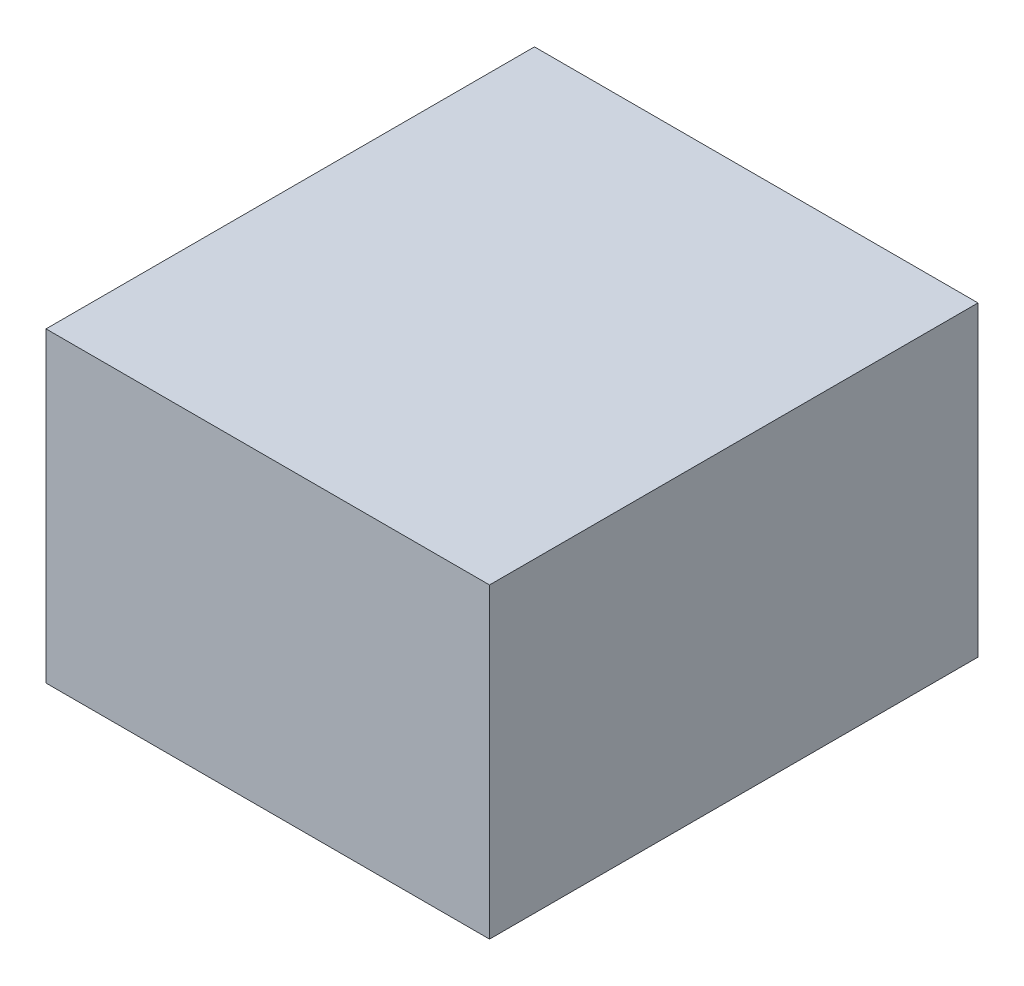
SolidWorks part; units mm, degrees
ref_plane "Front Plane" through (0, 0, 0) normal (0, 0, 1) x (1, 0, 0)
ref_plane "Top Plane" through (0, 0, 0) normal (0, 1, 0) x (1, 0, 0)
ref_plane "Right Plane" through (0, 0, 0) normal (1, 0, 0) x (0, 0, -1)
sketch "Sketch1" plane through (0, 0, 0) normal (0, 1, 0) x (1, 0, 0)
  line L1 (-45.4, -50) -> (45.4, -50)
  line L2 (-45.4, -50) -> (-45.4, 50)
  line L3 (-45.4, 50) -> (45.4, 50)
  line L4 (45.4, -50) -> (45.4, 50)
  line L5 (-45.4, -50) -> (45.4, 50) construction
  line L6 (-45.4, 50) -> (45.4, -50) construction
  point P0 (0, 0)
extrude "Boss-Extrude1" add sketch "Sketch1" along normal blind 62.8
sketch "Sketch2" plane through (0, 0, 0) normal (0, -1, 0) x (-1, 0, 0)
  line L1 (33.5507, -1.55) -> (33.5507, -5.4485)
  line L4 (-30.4478, 1.55) -> (-30.4478, 5.4485)
  line L12 (-30.4478, -5.4485) -> (-30.4478, -1.55)
  line L13 (-31.9993, 7) -> (-32, 7)
  line L14 (-33.5507, 5.4485) -> (-33.5507, 1.55)
  line L15 (-32, -7) -> (-31.9985, -7)
  line L17 (-33.5507, -1.55) -> (-33.5507, -5.4485)
  line L19 (-26.55, 1.55) -> (-30.4478, 1.55)
  line L21 (-37.45, -1.55) -> (-33.5507, -1.55)
  line L22 (-30.4478, -1.55) -> (-26.55, -1.55)
  line L23 (-33.5507, 1.55) -> (-37.45, 1.55)
  line L28 (37.45, -1.55) -> (33.5507, -1.55)
  line L29 (33.5507, 1.55) -> (37.45, 1.55)
  line L30 (33.5507, 5.4485) -> (33.5507, 1.55)
  line L31 (30.4478, 1.55) -> (30.4478, 5.4485)
  line L32 (26.55, 1.55) -> (30.4478, 1.55)
  line L33 (30.4478, -1.55) -> (26.55, -1.55)
  line L34 (30.4478, -5.4485) -> (30.4478, -1.55)
  arc A0 (-33.5507, -5.4485) -> (-30.4478, -5.4485) centre (-31.9993, -5.4485) ccw
  arc A1 (-33.5507, 5.4485) -> (-30.4478, 5.4485) centre (-31.9993, 5.4485) cw
  arc A2 (-26.55, -1.55) -> (-26.55, 1.55) centre (-26.55, 0) ccw
  arc A3 (-37.45, -1.55) -> (-37.45, 1.55) centre (-37.45, 0) cw
  arc A4 (33.5507, -5.4485) -> (30.4478, -5.4485) centre (31.9993, -5.4485) cw
  arc A5 (37.45, -1.55) -> (37.45, 1.55) centre (37.45, 0) ccw
  arc A6 (33.5507, 5.4485) -> (30.4478, 5.4485) centre (31.9993, 5.4485) ccw
  arc A7 (26.55, -1.55) -> (26.55, 1.55) centre (26.55, 0) cw
extrude "Cut-Extrude2" cut sketch "Sketch2" against normal blind 50 contours L4 A1 L14 L23 A3 L21 L17 A0 L12 L22 A2 L19 | L30 L29 A5 L28 L1 A4 L34 L33 A7 L32 L31 A6
sketch "Sketch3" plane through (0, 0, 0) normal (0, -1, 0) x (1, 0, 0)
  circle A2 centre (31.9993, 35.35) radius 3.25
  circle A3 centre (31.9993, -35.35) radius 3.25
  circle A4 centre (-31.9993, -35.35) radius 3.25
  circle A5 centre (-31.9993, 35.35) radius 3.25
extrude "Boss-Extrude2" add sketch "Sketch3" along normal blind 1.8
fillet "Fillet3" radius 1.8 4 edges at (-31.9993, -1.8, -32.1) (-31.9993, -1.8, 38.6) (31.9993, -1.8, 32.1) (31.9993, -1.8, -38.6)
sketch "Sketch4" plane through (0, 0, 0) normal (0, -1, 0) x (-1, 0, 0)
  circle A0 centre (18.65, -44.25) radius 2.25
  circle A1 centre (-39.15, -44.25) radius 2.25
  circle A2 centre (-39.15, 44.25) radius 2.25
  circle A3 centre (18.65, 44.25) radius 2.25
extrude "Boss-Extrude3" add sketch "Sketch4" along normal blind 0.5
sketch "Sketch6" plane through (-45.4, 0, 0) normal (-1, 0, 0) x (0, 0, 1)
  circle A0 centre (24.75, 49.55) radius 6.75
extrude "Boss-Extrude4" add sketch "Sketch6" along normal blind 2.2
chamfer "Chamfer2" distance 1.4 angle 45 1 edges at (-47.6, 49.55, 31.5)
